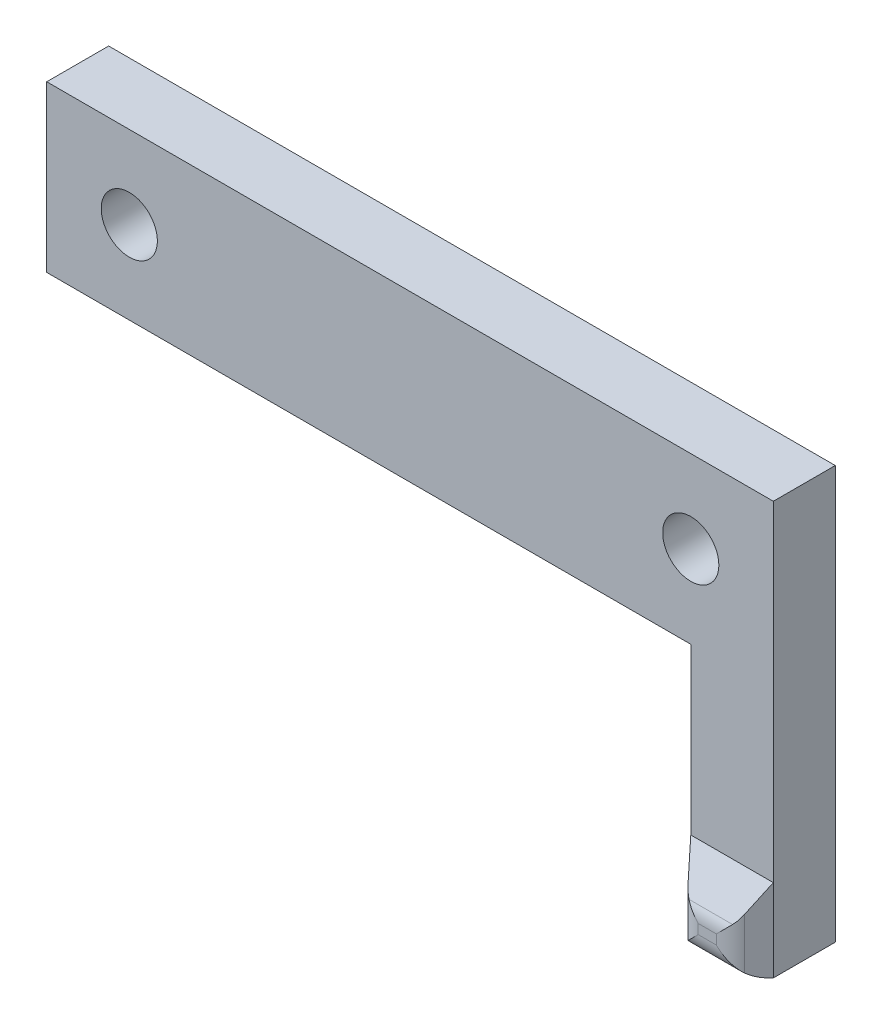
SolidWorks part; units mm, degrees
ref_plane "Front Plane" through (0, 0, 0) normal (0, 0, 1) x (1, 0, 0)
ref_plane "Top Plane" through (0, 0, 0) normal (0, 1, 0) x (1, 0, 0)
ref_plane "Right Plane" through (0, 0, 0) normal (1, 0, 0) x (0, 0, -1)
sketch "Sketch1" plane through (0, 0, 0) normal (0, 0, 1) x (1, 0, 0)
  line L0 (0, 0) -> (68, 0) construction
  line L2 (78, 10) -> (-10, 10)
  line L3 (78, 10) -> (78, -10)
  line L4 (78, -10) -> (-10, -10)
  line L5 (-10, 10) -> (-10, -10)
  line L6 (78, 10) -> (-10, -10) construction
  line L7 (78, -10) -> (-10, 10) construction
  circle A0 centre (0, 0) radius 3.4
  circle A1 centre (68, 0) radius 3.4
  point P5 (34, 0)
  dimension "D2" = 6.8
  dimension "D3" = 10
  dimension "D1" = 68
  dimension "D4" = 10
extrude "Boss-Extrude1" add sketch "Sketch1" along normal blind 7.5
sketch "Sketch2" plane through (0, -10, 0) normal (0, -1, 0) x (1, 0, 0)
  line L0 (68, 0) -> (78, 0)
  line L1 (78, 0) -> (78, 7.5)
  line L2 (-10, 7.5) -> (78, 7.5) construction
  line L3 (78, 7.5) -> (68, 7.5)
  line L4 (68, 7.5) -> (68, 0)
  line L5 (78, 7.5) -> (78, 0) construction
  dimension "D1" = 10
extrude "Boss-Extrude2" add sketch "Sketch2" along normal blind 30
ref_plane "Plane1" through (0, 0, 10.5) normal (0, 0, 1) x (1, 0, 0)
sketch "Sketch3" plane through (0, 0, 10.5) normal (0, 0, 1) x (1, 0, 0)
  line L0 (78, -40) -> (68, -30) construction
  line L2 (68, -30) -> (68, -40) construction
  line L3 (73, -35) -> (73, -40) construction
  line L4 (75.5, -35) -> (70.5, -35)
  line L5 (75.5, -35) -> (75.5, -40)
  line L6 (75.5, -40) -> (70.5, -40)
  line L7 (70.5, -35) -> (70.5, -40)
  line L8 (75.5, -35) -> (70.5, -40) construction
  line L9 (75.5, -40) -> (70.5, -35) construction
  line L10 (78, -40) -> (68, -40) construction
  point P5 (73, -37.5)
  point P13 (73, -35)
  dimension "D1" = 10
  dimension "D2" = 5
sketch "Sketch4" plane through (0, 0, 7.5) normal (0, 0, 1) x (1, 0, 0)
  line L0 (68, -30) -> (78, -40) construction
  line L2 (78, -40) -> (68, -40)
  line L3 (78, -40) -> (78, -30)
  line L4 (78, -30) -> (68, -30)
  line L5 (68, -40) -> (68, -30)
  dimension "D1" = 10
loft "Loft1" add profiles "Sketch4", "Sketch3" connector at (68, -30, 7.5) connector at (70.5, -35, 10.5)
fillet "Fillet1" radius 3 4 edges
